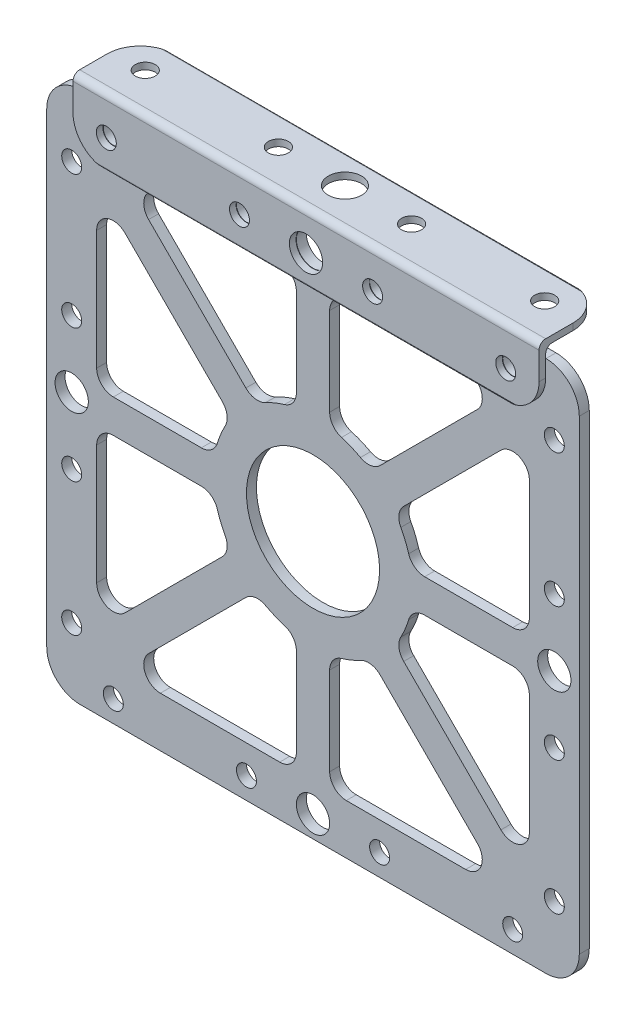
SolidWorks part; units mm, degrees
material "Fibra de vidrio-A"
ref_plane "Alzado" through (0, 0, 0) normal (0, 0, 1) x (1, 0, 0)
ref_plane "Planta" through (0, 0, 0) normal (0, 1, 0) x (1, 0, 0)
ref_plane "Vista lateral" through (0, 0, 0) normal (1, 0, 0) x (0, 0, -1)
sketch "Croquis1" plane through (0, 0, 0) normal (0, 0, 1) x (1, 0, 0)
  line L1 (-35, -40) -> (35, -40)
  line L2 (-40, -35) -> (-40, 35)
  line L3 (-35, 40) -> (35, 40)
  line L4 (40, -35) -> (40, 35)
  line L5 (-40, -40) -> (40, 40) construction
  line L6 (-40, 40) -> (40, -40) construction
  arc A0 (35, 40) -> (40, 35) centre (35, 35) cw
  arc A1 (35, -40) -> (40, -35) centre (35, -35) ccw
  arc A2 (-35, -40) -> (-40, -35) centre (-35, -35) cw
  arc A3 (-40, 35) -> (-35, 40) centre (-35, 35) cw
  point P0 (0, 0)
  dimension "D2" = 5
  dimension "D1" = 80
extrude "Saliente-Extruir1" add sketch "Croquis1" along normal blind 1.5
sketch "Croquis2" plane through (0, 0, 1.5) normal (0, 0, 1) x (1, 0, 0)
  line L0 (0, 0) -> (0, 40) construction
  line L1 (35, 40) -> (-35, 40) construction
  line L2 (0, 0) -> (40, 0) construction
  line L3 (40, -35) -> (40, 35) construction
  line L4 (2.5, 16.7705) -> (2.5, 30)
  line L5 (0, 0) -> (38.5355, 38.5355) construction
  line L6 (10.0908, 13.6263) -> (24.6967, 28.2322)
  line L7 (5, 32.5) -> (22.9289, 32.5)
  line L8 (-10.0908, 13.6263) -> (-24.6967, 28.2322)
  line L9 (-5, 32.5) -> (-22.9289, 32.5)
  line L10 (-2.5, 16.7705) -> (-2.5, 30)
  line L11 (32.5, 5) -> (32.5, 22.9289)
  line L12 (16.7705, 2.5) -> (30, 2.5)
  line L13 (13.6263, 10.0908) -> (28.2322, 24.6967)
  line L14 (16.7705, -2.5) -> (30, -2.5)
  line L15 (32.5, -5) -> (32.5, -22.9289)
  line L16 (13.6263, -10.0908) -> (28.2322, -24.6967)
  line L17 (5, -32.5) -> (22.9289, -32.5)
  line L18 (2.5, -16.7705) -> (2.5, -30)
  line L19 (10.0908, -13.6263) -> (24.6967, -28.2322)
  line L20 (-2.5, -16.7705) -> (-2.5, -30)
  line L21 (-5, -32.5) -> (-22.9289, -32.5)
  line L22 (-10.0908, -13.6263) -> (-24.6967, -28.2322)
  line L23 (-32.5, -5) -> (-32.5, -22.9289)
  line L24 (-16.7705, -2.5) -> (-30, -2.5)
  line L25 (-13.6263, -10.0908) -> (-28.2322, -24.6967)
  line L26 (-16.7705, 2.5) -> (-30, 2.5)
  line L27 (-32.5, 5) -> (-32.5, 22.9289)
  line L28 (-13.6263, 10.0908) -> (-28.2322, 24.6967)
  circle A0 centre (0, 0) radius 10
  arc A1 (7.134, 13.1949) -> (4.2857, 14.3747) centre (0, 0) ccw
  arc A2 (40, 35) -> (35, 40) centre (35, 35) ccw construction
  circle A3 centre (0, 0) radius 15 construction
  arc A4 (2.5, 16.7705) -> (4.2857, 14.3747) centre (5, 16.7705) ccw
  arc A5 (10.0908, 13.6263) -> (7.134, 13.1949) centre (8.323, 15.3941) cw
  arc A6 (24.6967, 28.2322) -> (22.9289, 32.5) centre (22.9289, 30) ccw
  arc A7 (2.5, 30) -> (5, 32.5) centre (5, 30) cw
  arc A8 (-24.6967, 28.2322) -> (-22.9289, 32.5) centre (-22.9289, 30) cw
  arc A9 (-2.5, 30) -> (-5, 32.5) centre (-5, 30) ccw
  arc A10 (-2.5, 16.7705) -> (-4.2857, 14.3747) centre (-5, 16.7705) cw
  arc A11 (-10.0908, 13.6263) -> (-7.134, 13.1949) centre (-8.323, 15.3941) ccw
  arc A12 (-7.134, 13.1949) -> (-4.2857, 14.3747) centre (0, 0) cw
  arc A13 (28.2322, 24.6967) -> (32.5, 22.9289) centre (30, 22.9289) cw
  arc A14 (30, 2.5) -> (32.5, 5) centre (30, 5) ccw
  arc A15 (16.7705, 2.5) -> (14.3747, 4.2857) centre (16.7705, 5) cw
  arc A16 (13.1949, 7.134) -> (14.3747, 4.2857) centre (0, 0) cw
  arc A17 (13.6263, 10.0908) -> (13.1949, 7.134) centre (15.3941, 8.323) ccw
  arc A18 (13.1949, -7.134) -> (14.3747, -4.2857) centre (0, 0) ccw
  arc A19 (13.6263, -10.0908) -> (13.1949, -7.134) centre (15.3941, -8.323) cw
  arc A20 (16.7705, -2.5) -> (14.3747, -4.2857) centre (16.7705, -5) ccw
  arc A21 (30, -2.5) -> (32.5, -5) centre (30, -5) cw
  arc A22 (28.2322, -24.6967) -> (32.5, -22.9289) centre (30, -22.9289) ccw
  arc A23 (24.6967, -28.2322) -> (22.9289, -32.5) centre (22.9289, -30) cw
  arc A24 (2.5, -30) -> (5, -32.5) centre (5, -30) ccw
  arc A25 (2.5, -16.7705) -> (4.2857, -14.3747) centre (5, -16.7705) cw
  arc A26 (7.134, -13.1949) -> (4.2857, -14.3747) centre (0, 0) cw
  arc A27 (10.0908, -13.6263) -> (7.134, -13.1949) centre (8.323, -15.3941) ccw
  arc A28 (-7.134, -13.1949) -> (-4.2857, -14.3747) centre (0, 0) ccw
  arc A29 (-10.0908, -13.6263) -> (-7.134, -13.1949) centre (-8.323, -15.3941) cw
  arc A30 (-2.5, -16.7705) -> (-4.2857, -14.3747) centre (-5, -16.7705) ccw
  arc A31 (-2.5, -30) -> (-5, -32.5) centre (-5, -30) cw
  arc A32 (-24.6967, -28.2322) -> (-22.9289, -32.5) centre (-22.9289, -30) ccw
  arc A33 (-28.2322, -24.6967) -> (-32.5, -22.9289) centre (-30, -22.9289) cw
  arc A34 (-30, -2.5) -> (-32.5, -5) centre (-30, -5) ccw
  arc A35 (-16.7705, -2.5) -> (-14.3747, -4.2857) centre (-16.7705, -5) cw
  arc A36 (-13.1949, -7.134) -> (-14.3747, -4.2857) centre (0, 0) cw
  arc A37 (-13.6263, -10.0908) -> (-13.1949, -7.134) centre (-15.3941, -8.323) ccw
  arc A38 (-13.1949, 7.134) -> (-14.3747, 4.2857) centre (0, 0) ccw
  arc A39 (-13.6263, 10.0908) -> (-13.1949, 7.134) centre (-15.3941, 8.323) cw
  arc A40 (-16.7705, 2.5) -> (-14.3747, 4.2857) centre (-16.7705, 5) ccw
  arc A41 (-30, 2.5) -> (-32.5, 5) centre (-30, 5) cw
  arc A42 (-28.2322, 24.6967) -> (-32.5, 22.9289) centre (-30, 22.9289) ccw
  point P25 (28.9645, 32.5)
  point P28 (2.5, 32.5)
  point P116 (0, 0)
  dimension "D1" = 20
  dimension "D7" = 2.5
  dimension "D2" = 5
  dimension "D3" = 7.5
  dimension "D4" = 2.5
  dimension "D5" = 5
  dimension "D8" = 4
extrude "Cortar-Extruir1" cut sketch "Croquis2" against normal through all
sketch "Croquis3" plane through (0, 0, 1.5) normal (0, 0, 1) x (1, 0, 0)
  line L0 (-36.25, -40) -> (-36.25, 40) construction
  line L1 (-40, 35) -> (-40, -35) construction
  line L2 (-40, 0) -> (-32.5, 0) construction
  line L3 (35, 40) -> (-35, 40) construction
  line L4 (0, -0.825) -> (0, 0.825) construction
  circle A0 centre (-36.25, 30) radius 1.5
  circle A1 centre (-36.25, 10) radius 1.5
  circle A2 centre (-36.25, -10) radius 1.5
  circle A3 centre (-36.25, -30) radius 1.5
  circle A4 centre (36.25, -30) radius 1.5
  circle A5 centre (36.25, -10) radius 1.5
  circle A6 centre (36.25, 10) radius 1.5
  circle A7 centre (36.25, 30) radius 1.5
  circle A8 centre (-36.25, 0) radius 2.5
  circle A9 centre (36.25, 0) radius 2.5
  point P8 (-36.25, 0)
  dimension "D1" = 3
  dimension "D2" = 10
  dimension "D4" = 5
  dimension "D3" = 4
extrude "Cortar-Extruir2" cut sketch "Croquis3" against normal through all
sketch "Croquis5" plane through (0, 0, 0) normal (1, 0, 0) x (0, 0, -1)
  line L0 (0, 32.5) -> (-1.5, 32.5) construction
  line L2 (-0.75, 32.5) -> (-0.75, 35) construction
  line L3 (-1.5, 35) -> (0, 35) construction
  line L4 (-1.55, 32.75) -> (-1.55, 40)
  line L5 (-1.8, 32.5) -> (-2.3, 32.5)
  line L6 (-2.55, 32.75) -> (-2.55, 40.85)
  line L7 (1.05, 32.75) -> (1.05, 40.85)
  line L8 (0.3, 32.5) -> (0.8, 32.5)
  line L9 (0.05, 32.75) -> (0.05, 40)
  line L10 (-1.3, 40.25) -> (-0.2, 40.25)
  line L11 (-2.05, 41.35) -> (0.55, 41.35)
  arc A0 (1.05, 40.85) -> (0.55, 41.35) centre (0.55, 40.85) ccw
  arc A1 (-2.55, 40.85) -> (-2.05, 41.35) centre (-2.05, 40.85) cw
  arc A2 (0.05, 40) -> (-0.2, 40.25) centre (-0.2, 40) ccw
  arc A3 (-1.55, 40) -> (-1.3, 40.25) centre (-1.3, 40) cw
  arc A4 (1.05, 32.75) -> (0.8, 32.5) centre (0.8, 32.75) cw
  arc A5 (0.3, 32.5) -> (0.05, 32.75) centre (0.3, 32.75) cw
  arc A6 (-1.8, 32.5) -> (-1.55, 32.75) centre (-1.8, 32.75) ccw
  arc A7 (-2.3, 32.5) -> (-2.55, 32.75) centre (-2.3, 32.75) cw
  point P16 (1.05, 41.35)
  point P19 (-2.55, 41.35)
  point P22 (0.05, 40.25)
  point P25 (-1.55, 40.25)
  point P28 (1.05, 32.5)
  point P31 (0.05, 32.5)
  point P34 (-1.55, 32.5)
  point P37 (-2.55, 32.5)
  dimension "D5" = 0.5
  dimension "D6" = 0.25
  dimension "D7" = 0.25
  dimension "D1" = 0.8
  dimension "D2" = 7.75
  dimension "D3" = 1
  dimension "D4" = 8.85
extrude "Saliente-Extruir2" add sketch "Croquis5" along normal mid plane 70 separate body
sketch "Croquis4" plane through (0, 0, 1.5) normal (0, 0, 1) x (1, 0, 0)
  line L0 (0, 40) -> (0, 36.75) construction
  line L1 (35, 40) -> (-35, 40) construction
  line L2 (-40, 36.75) -> (40, 36.75) construction
  line L3 (1.98, 0) -> (-1.98, 0) construction
  circle A0 centre (-30, 36.75) radius 1.5
  circle A1 centre (-10, 36.75) radius 1.5
  circle A2 centre (10, 36.75) radius 1.5
  circle A3 centre (30, 36.75) radius 1.5
  circle A4 centre (10, -36.75) radius 1.5
  circle A5 centre (30, -36.75) radius 1.5
  circle A6 centre (-10, -36.75) radius 1.5
  circle A7 centre (-30, -36.75) radius 1.5
  circle A8 centre (0, 36.75) radius 2.5
  circle A9 centre (0, -36.75) radius 2.5
  point P8 (0, 36.75)
  dimension "D3" = 3
  dimension "D6" = 5
  dimension "D1" = 3.25
  dimension "D2" = 40
  dimension "D4" = 10
  dimension "D5" = 4
extrude "Cortar-Extruir3" cut sketch "Croquis4" against normal through all both and the other way through all
fillet "Redondeo1" radius 5 4 edges at (-35, 32.5, -0.55) (35, 32.5, -0.55) (35, 32.5, 2.05) (-35, 32.5, 2.05)
pattern_circular "MatrizC1" count 2 every 90 about axis through (0, 40.8, 0.75) along (1, 0, 0) of bodies 106
combine bodies "Combinar2" bodies to combine 106 107
sketch "Croquis6" plane through (35, 0, 0) normal (1, 0, 0) x (0, 0, -1)
  line L0 (-2.55, 40.85) -> (-2.55, 41.6)
  line L1 (-1.55, 42.6) -> (-0.8, 42.6)
  line L2 (-0.8, 42.6) -> (-0.8, 40.85)
  line L3 (-0.8, 40.85) -> (-2.55, 40.85)
  arc A0 (-2.55, 41.6) -> (-1.55, 42.6) centre (-1.55, 41.6) cw
  dimension "D1" = 1
extrude "Saliente-Extruir3" add sketch "Croquis6" against normal up to surface (70 mm away) up to face at (-35, 40.1525, 0.1025)
sketch "Croquis7" plane through (35, 0, 0) normal (1, 0, 0) x (0, 0, -1)
  line L9 (0.05, 37.5) -> (0.05, 39)
  line L10 (1.05, 40) -> (2.55, 40)
  line L11 (2.55, 40) -> (2.55, 41.6)
  line L12 (2.55, 41.6) -> (-0.55, 41.6)
  line L13 (-1.55, 40.6) -> (-1.55, 37.5)
  line L14 (-1.55, 37.5) -> (0.05, 37.5)
  arc A0 (-0.55, 41.6) -> (-1.55, 40.6) centre (-0.55, 40.6) ccw
  arc A1 (0.05, 39) -> (1.05, 40) centre (1.05, 39) cw
  point P21 (0.05, 40)
  dimension "D1" = 1
extrude "Cortar-Extruir4" cut sketch "Croquis7" against normal through all
delete or keep bodies "Sólido-Eliminar/Conservar 3" bodies 113
